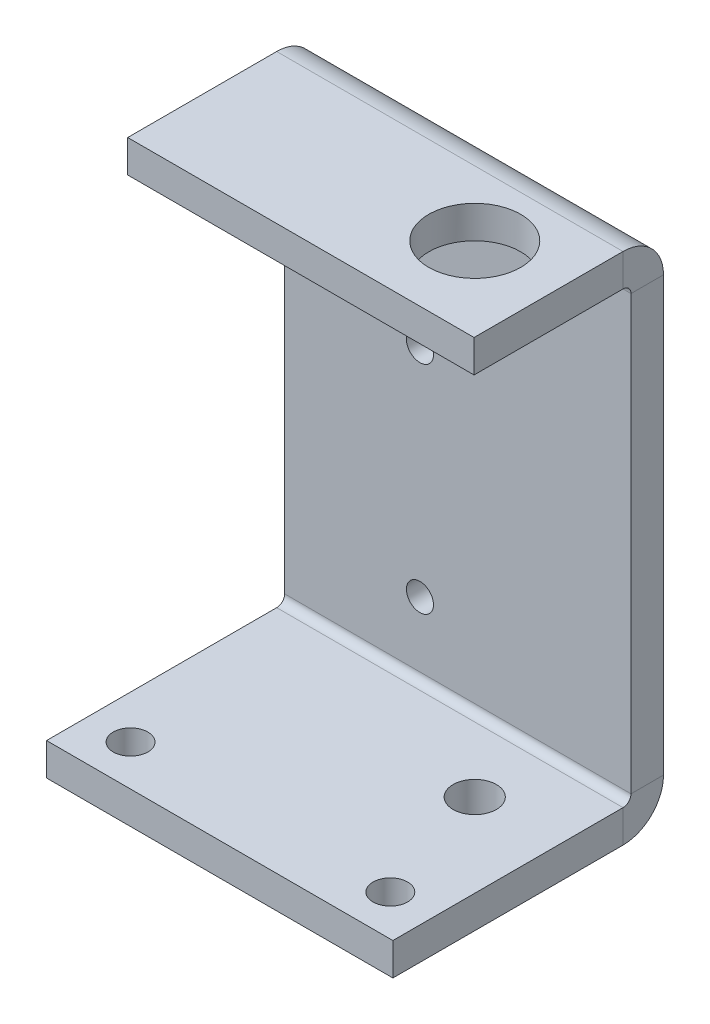
SolidWorks part; units mm, degrees
note: The reader was unsure of these and kept them because the rebuilt part matched: flange length of "Edge-Flange1", "Edge-Flange2".
material "AISI 1045 Steel, cold drawn"
ref_plane "Front Plane" through (0, 0, 0) normal (0, 0, 1) x (1, 0, 0)
ref_plane "Top Plane" through (0, 0, 0) normal (0, 1, 0) x (1, 0, 0)
ref_plane "Right Plane" through (0, 0, 0) normal (1, 0, 0) x (0, 0, -1)
sketch "Sketch1" plane through (0, 0, 0) normal (0, 1, 0) x (1, 0, 0)
  line L1 (16, -12.5) -> (-16, -12.5)
  line L2 (16, -12.5) -> (16, 12.5)
  line L3 (16, 12.5) -> (-16, 12.5)
  line L4 (-16, -12.5) -> (-16, 12.5)
  line L5 (16, -12.5) -> (-16, 12.5) construction
  line L6 (16, 12.5) -> (-16, -12.5) construction
  point P0 (0, 0)
  dimension "D1" = 32
  dimension "D2" = 25
base flange "Base-Flange1" sketch "Sketch1" thickness 3 reverse thickness direction no parameters "D1"=0.7366
edge flange "Edge-Flange1" sketch "Sketch8" flange angle 90 flange length 47.5 bend radius 0.7366 thickness 3 relief rectangular parameters "D6"=10
sketch "Sketch8" plane through (0, 0, -12.5) normal (0, 0, -1) x (-1, 0, 0)
  line L2 (-16, 0) -> (-16, 44.5)
  line L3 (-16, 44.5) -> (16, 44.5)
  line L4 (16, 44.5) -> (16, 0)
  line L7 (-16, 0) -> (16, 0) construction
  line L8 (-16, 0) -> (16, 0)
  dimension "D1" = 44.5
bend "EdgeBend1" bend radius 0.7366 bend angle 90 parameters "D5"=1
edge flange "Edge-Flange2" sketch "Sketch13" flange angle 90 flange length 17.5 bend radius 0.7366 thickness 3 relief rectangular parameters "D6"=10
sketch "Sketch13" plane through (0, 44.5, -9.5) normal (0, 1, 0) x (-1, 0, 0)
  line L2 (-16, 0) -> (-16, 14.5)
  line L3 (-16, 14.5) -> (16, 14.5)
  line L4 (16, 14.5) -> (16, 0)
  line L7 (16, 0) -> (-16, 0) construction
  line L8 (16, 0) -> (-16, 0)
bend "EdgeBend2" bend radius 0.7366 bend angle 90 parameters "D5"=2
hole_wizard "Tap Drill for M3x0.5 Tap1" positions "Sketch14" profile "Sketch15" hole size "M3x0.5" standard "ANSI Metric" end condition through all
sketch "Sketch14" plane through (0, 0, -9.5) normal (0, 0, 1) x (1, 0, 0)
  line L0 (16, 0.7366) -> (-16, 0.7366) construction
  line L1 (-16, 0.7366) -> (-16, 40.7634) construction
  point P0 (-3.5, 6.7366)
  point P2 (-3.5, 26.7366)
  point P8 (0, 0)
  dimension "D1" = 6
  dimension "D2" = 12.5
  dimension "D3" = 20
sketch "Sketch15" plane through (-3.5, 6.7366, -9.5) normal (1, 0, 0) x (0, -1, 0)
  line L0 (0, 0) -> (0, 3)
  line L1 (0, 3) -> (1.25, 3)
  line L2 (1.25, 3) -> (1.25, 0)
  line L5 (1.25, 0) -> (0, 0)
  line L11 (0, -6.35) -> (0, 107.95) construction
  dimension "Thru Hole Dia." = 2.5
  dimension "Thru Hole Depth" = 3
hole_wizard "Tap Drill for M10x1.5 Tap2" positions "Sketch18" profile "Sketch19" hole size "M10x1.5" standard "ANSI Metric" end condition up to next
sketch "Sketch18" plane through (0, 44.5, 0) normal (0, 1, 0) x (1, 0, 0)
  line L0 (-16, 8.7634) -> (-16, -5) construction
  line L1 (-16, 8.7634) -> (16, 8.7634) construction
  point P0 (8.3, 2.7634)
  dimension "D1" = 24.3
  dimension "D2" = 6
sketch "Sketch19" plane through (8.3, 44.5, -2.7634) normal (1, 0, 0) x (0, 0, 1)
  line L0 (0, 0) -> (0, 3)
  line L1 (0, 3) -> (4.25, 3)
  line L2 (4.25, 3) -> (4.25, 0)
  line L5 (4.25, 0) -> (0, 0)
  line L11 (0, -6.35) -> (0, 107.95) construction
  dimension "Thru Hole Dia." = 8.5
  dimension "Thru Hole Depth" = 3
hole_wizard "M3 Clearance Hole1" positions "Sketch20" profile "Sketch21" hole size "M3" standard "ANSI Metric" end condition up to next
sketch "Sketch20" plane through (0, 0, 0) normal (0, 1, 0) x (1, 0, 0)
  line L2 (-16, 8.7634) -> (-16, -12.5) construction
  line L3 (16, -12.5) -> (16, 8.7634) construction
  line L4 (-16, 8.7634) -> (16, 8.7634) construction
  point P0 (-12, -8.7366)
  point P2 (12, -8.7366)
  dimension "D1" = 17.5
  dimension "D2" = 4
  dimension "D3" = 4
sketch "Sketch21" plane through (-12, 0, 8.7366) normal (1, 0, 0) x (0, 0, 1)
  line L0 (0, 0) -> (0, 3)
  line L1 (0, 3) -> (1.6, 3)
  line L2 (1.6, 3) -> (1.6, 0)
  line L5 (1.6, 0) -> (0, 0)
  line L11 (0, -6.35) -> (0, 107.95) construction
  dimension "Thru Hole Dia." = 3.2
  dimension "Thru Hole Depth" = 3
hole_wizard "Ø4.0 (4) Diameter Hole1" positions "Sketch22" profile "Sketch23" hole size "Ø4.0" standard "ANSI Metric" end condition up to next
sketch "Sketch22" plane through (0, 0, 0) normal (0, 1, 0) x (1, 0, 0)
  point P0 (8.3, 2.7634)
  point P4 (8.3, 2.7634)
sketch "Sketch23" plane through (8.3, 0, -2.7634) normal (1, 0, 0) x (0, 0, 1)
  line L0 (0, 0) -> (0, 3)
  line L1 (0, 3) -> (2, 3)
  line L2 (2, 3) -> (2, 0)
  line L5 (2, 0) -> (0, 0)
  line L11 (0, -6.35) -> (0, 107.95) construction
  dimension "Thru Hole Dia." = 4
  dimension "Thru Hole Depth" = 3
sketch "Bend-Lines1" [suppressed] plane through (0, 0, 0) normal (0, 1, 0) x (1, 0, 0)
sketch "Bounding-Box1" [suppressed] plane through (0, 0, 0) normal (0, 1, 0) x (1, 0, 0)
sheet metal parameters "Sheet-Metal1" thickness 3 parameters "D1"=0.7366
flat pattern "Flat-Pattern1" [suppressed]
sketch "Bend-Lines2" plane through (0, 0, 0) normal (0, 1, 0) x (1, 0, 0)
sketch3d "Bounding-Box2" [suppressed]
  line L0 (45.7557, 78.7423, 0) -> (45.7557, -78.7423, 0) construction
  line L1 (-45.7557, 78.7423, 0) -> (-45.7557, -78.7423, 0) construction
  line L2 (45.7557, 78.7423, 0) -> (-45.7557, 78.7423, 0) construction
  line L3 (45.7557, -78.7423, 0) -> (-45.7557, -78.7423, 0) construction
sheet metal parameters "Sheet-Metal2" thickness 3 parameters "D1"=0.7366
flat pattern "Flat-Pattern1"
sketch "Bend-Lines2" plane through (0, 0, 0) normal (0, 1, 0) x (1, 0, 0)
  line L0 (15, 10.52) -> (-15, 10.52) construction
  line L1 (15, 10.52) -> (-15, 10.52) construction
sketch3d "Bounding-Box2" [suppressed]
  line L0 (-15, 61.54, 0) -> (-15, -12.5, 0) construction
  line L1 (15, 61.54, 0) -> (15, -12.5, 0) construction
  line L2 (-15, 61.54, 0) -> (15, 61.54, 0) construction
  line L3 (-15, -12.5, 0) -> (15, -12.5, 0) construction
bend of the flat pattern "Flatten-<EdgeBend1>1"
sheet metal parameters "Sheet-Metal4" thickness 3 parameters "D1"=0.7366
flat pattern "Flat-Pattern1"
sketch "Bend-Lines2" plane through (0, 0, 0) normal (0, 1, 0) x (1, 0, 0)
  line L0 (15, 10.52) -> (-15, 10.52) construction
  line L1 (15, 10.52) -> (-15, 10.52) construction
  line L2 (15, 62.5601) -> (-15, 62.5601) construction
  line L3 (15, 62.5601) -> (-15, 62.5601) construction
sketch3d "Bounding-Box2" [suppressed]
  line L0 (-15, 85.5801, 0) -> (-15, -12.5, 0) construction
  line L1 (15, 85.5801, 0) -> (15, -12.5, 0) construction
  line L2 (-15, 85.5801, 0) -> (15, 85.5801, 0) construction
  line L3 (-15, -12.5, 0) -> (15, -12.5, 0) construction
bend of the flat pattern "Flatten-<EdgeBend1>1"
bend of the flat pattern "Flatten-<EdgeBend2>1"
sheet metal parameters "Sheet-Metal5" thickness 3 parameters "D1"=0.7366
flat pattern "Flat-Pattern1"
sketch "Bend-Lines2" plane through (0, 0, 0) normal (0, 1, 0) x (1, 0, 0)
  line L0 (15, 10.52) -> (-15, 10.52) construction
  line L1 (15, 10.52) -> (-15, 10.52) construction
  line L2 (15, 62.5601) -> (-15, 62.5601) construction
  line L3 (15, 62.5601) -> (-15, 62.5601) construction
sketch3d "Bounding-Box2" [suppressed]
  line L0 (-15, 85.5801, 0) -> (-15, -12.5, 0) construction
  line L1 (15, 85.5801, 0) -> (15, -12.5, 0) construction
  line L2 (-15, 85.5801, 0) -> (15, 85.5801, 0) construction
  line L3 (-15, -12.5, 0) -> (15, -12.5, 0) construction
bend of the flat pattern "Flatten-<EdgeBend1>1"
bend of the flat pattern "Flatten-<EdgeBend2>1"
sheet metal parameters "Sheet-Metal6" thickness 3 parameters "D1"=0.7366
flat pattern "Flat-Pattern1"
sketch "Bend-Lines2" plane through (0, 0, 0) normal (0, 1, 0) x (1, 0, 0)
  line L0 (16, 10.52) -> (-16, 10.52) construction
  line L1 (16, 10.52) -> (-16, 10.52) construction
  line L2 (16, 54.0601) -> (-16, 54.0601) construction
  line L3 (16, 54.0601) -> (-16, 54.0601) construction
sketch3d "Bounding-Box2" [suppressed]
  line L0 (-16, 69.5801, 0) -> (-16, -12.5, 0) construction
  line L1 (16, 69.5801, 0) -> (16, -12.5, 0) construction
  line L2 (-16, 69.5801, 0) -> (16, 69.5801, 0) construction
  line L3 (-16, -12.5, 0) -> (16, -12.5, 0) construction
bend of the flat pattern "Flatten-<EdgeBend1>1"
bend of the flat pattern "Flatten-<EdgeBend2>1"
sheet metal parameters "Sheet-Metal7" thickness 3 parameters "D1"=0.7366
flat pattern "Flat-Pattern1"
sketch "Bend-Lines2" plane through (0, 0, 0) normal (0, 1, 0) x (1, 0, 0)
  line L0 (16, 10.52) -> (-16, 10.52) construction
  line L1 (16, 10.52) -> (-16, 10.52) construction
  line L2 (16, 54.0601) -> (-16, 54.0601) construction
  line L3 (16, 54.0601) -> (-16, 54.0601) construction
sketch3d "Bounding-Box2" [suppressed]
  line L0 (-16, 69.5801, 0) -> (-16, -12.5, 0) construction
  line L1 (16, 69.5801, 0) -> (16, -12.5, 0) construction
  line L2 (-16, 69.5801, 0) -> (16, 69.5801, 0) construction
  line L3 (-16, -12.5, 0) -> (16, -12.5, 0) construction
bend of the flat pattern "Flatten-<EdgeBend1>1"
bend of the flat pattern "Flatten-<EdgeBend2>1"
sheet metal parameters "Sheet-Metal8" thickness 3 parameters "D1"=0.7366
flat pattern "Flat-Pattern1"
sketch "Bend-Lines2" plane through (0, 0, 0) normal (0, 1, 0) x (1, 0, 0)
  line L0 (16, 10.52) -> (-16, 10.52) construction
  line L1 (16, 10.52) -> (-16, 10.52) construction
  line L2 (16, 54.0601) -> (-16, 54.0601) construction
  line L3 (16, 54.0601) -> (-16, 54.0601) construction
sketch3d "Bounding-Box2" [suppressed]
  line L0 (-16, 69.5801, 0) -> (-16, -12.5, 0) construction
  line L1 (16, 69.5801, 0) -> (16, -12.5, 0) construction
  line L2 (-16, 69.5801, 0) -> (16, 69.5801, 0) construction
  line L3 (-16, -12.5, 0) -> (16, -12.5, 0) construction
bend of the flat pattern "Flatten-<EdgeBend1>1"
bend of the flat pattern "Flatten-<EdgeBend2>1"
